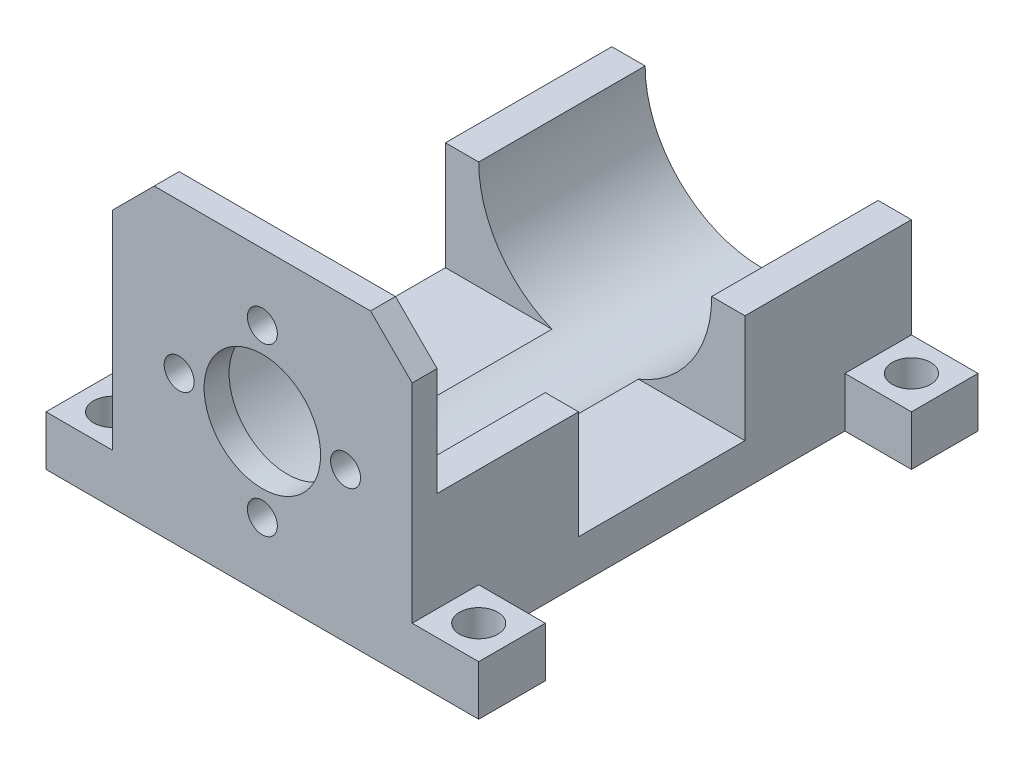
SolidWorks part; units mm, degrees
note: The reader was unsure of these and kept them because the rebuilt part matched: shared geometry of "Esquisse1<3>".
ref_plane "Plan de face" through (0, 0, 0) normal (0, 0, 1) x (1, 0, 0)
ref_plane "Plan de dessus" through (0, 0, 0) normal (0, 1, 0) x (1, 0, 0)
ref_plane "Plan de droite" through (0, 0, 0) normal (1, 0, 0) x (0, 0, -1)
sketch "Esquisse1" plane through (0, 0, 0) normal (0, 0, 1) x (1, 0, 0)
  line L0 (0, 0) -> (-10, 0) construction
  line L1 (-10, 0) -> (10, 0) construction
  line L2 (10, 0) -> (0, 0) construction
  line L3 (0, 0) -> (0, 10) construction
  line L4 (0, 0) -> (0, -10) construction
  line L5 (-18, 0) -> (-18, -18)
  line L6 (-18, -18) -> (0, -18)
  line L7 (0, -18) -> (18, -18)
  line L8 (18, -18) -> (18, 0)
  line L10 (18, 18) -> (-18, 18)
  line L11 (-18, 18) -> (-18, 0)
  line L12 (-18, 18) -> (-18, 13)
  line L13 (-18, 13) -> (-18, 18)
  line L14 (-18, 18) -> (-13, 18)
  line L15 (-13, 18) -> (-18, 13)
  line L16 (18, 18) -> (13, 18)
  line L17 (13, 18) -> (18, 18)
  line L18 (18, 18) -> (18, 13)
  line L19 (18, 13) -> (18, 0)
  line L20 (13, 18) -> (18, 13)
  line L21 (-18, 0) -> (-14, 0)
  line L22 (18, 0) -> (14, 0)
  circle A0 centre (0, 0) radius 14
  circle A1 centre (0, 0) radius 18
  circle A2 centre (-10, 0) radius 1.8
  circle A3 centre (0, 10) radius 1.8
  circle A4 centre (10, 0) radius 1.8
  circle A5 centre (0, -10) radius 1.8
  circle A6 centre (0, 0) radius 7
extrude "Boss.-Extru.1" add sketch "Esquisse1" against normal blind 60 contours A1 L7 L8 | A1 L5 L6 | L21 A1 L22 A0
extrude "Boss.-Extru.2" add sketch "Esquisse1<3>" against normal blind 3 contours A0 A5 A4 A3 A2 | L22 A1 L21 A0 | A1 L19 L20 L10 | A1 L10 L15 L11
sketch "Esquisse1<3>" plane through (0, 0, 0) normal (0, 0, 1) x (1, 0, 0) same geometry as "Esquisse1"
sketch "Esquisse2" plane through (0, -18, 0) normal (0, -1, 0) x (1, 0, 0)
  line L3 (18, -60) -> (26, -60)
  line L5 (-18, -60) -> (-26, -60)
  line L6 (-26, -60) -> (-26, -52)
  line L7 (-26, -52) -> (-18, -52)
  line L8 (-18, -52) -> (-18, -60)
  line L12 (26, -60) -> (26, -52)
  line L14 (-26, -52) -> (-18, -60) construction
  line L15 (-18, -52) -> (-26, -60) construction
  line L16 (-26, -8) -> (-18, -8)
  line L17 (-18, -8) -> (-26, -8)
  line L18 (-26, -8) -> (-26, 0)
  line L19 (18, 0) -> (26, 0)
  line L23 (-18, -60) -> (-18, 0) construction
  line L25 (26, 0) -> (26, -8)
  line L26 (26, -8) -> (18, -8)
  line L27 (18, -60) -> (18, 0) construction
  line L28 (18, -8) -> (18, 0)
  line L29 (26, -52) -> (18, -52)
  line L30 (-18, 0) -> (-26, 0)
  line L33 (-18, -16) -> (-18, 0)
  line L34 (-26, 0) -> (-26, -8) construction
  line L35 (18, -52) -> (18, -60)
  line L36 (-18, -8) -> (-26, 0) construction
  line L37 (-18, 0) -> (-26, -8) construction
  line L38 (18, -52) -> (26, -60) construction
  line L39 (26, -52) -> (18, -60) construction
  line L41 (18, 0) -> (26, -8) construction
  line L42 (18, -8) -> (26, 0) construction
  circle A5 centre (-22, -56) radius 2.3
  circle A8 centre (-22, -4) radius 2.3
  circle A9 centre (22, -4) radius 2.3
  circle A11 centre (22, -56) radius 2.3
sketch "Esquisse3" plane through (-18, 0, 0) normal (-1, 0, 0) x (0, 0, 1)
  line L0 (-60, -18) -> (0, -18) construction
  line L1 (-30, -18) -> (-30, 0) construction
  line L2 (-60, 0) -> (-3, 0) construction
  line L3 (-30, 0) -> (-20, 0)
  line L4 (-30, 0) -> (-40, 0)
  line L5 (-40, 0) -> (-40, -18) construction
  line L6 (-40, -18) -> (-30, -18) construction
  line L7 (-30, -18) -> (-20, -18) construction
  line L8 (-20, -18) -> (-20, 0) construction
  line L9 (-40, -18) -> (-40, -13) construction
  line L10 (-40, -13) -> (-20, -13)
  line L11 (-20, -13) -> (-20, 0)
  line L12 (-40, -13) -> (-40, 0)
extrude "Enlèv. mat.-Extru.2" cut sketch "Esquisse3" against normal blind 50
extrude "Boss.-Extru.4" add sketch "Esquisse2" against normal blind 6
